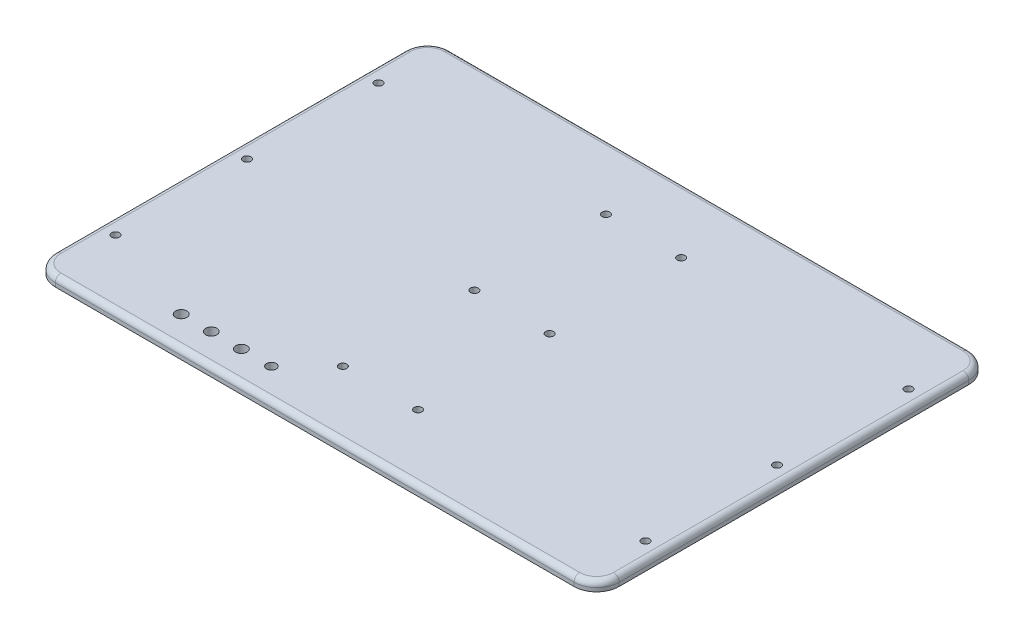
SolidWorks part; units mm, degrees
ref_plane "Front Plane" through (0, 0, 0) normal (0, 0, 1) x (1, 0, 0)
ref_plane "Top Plane" through (0, 0, 0) normal (0, 1, 0) x (1, 0, 0)
ref_plane "Right Plane" through (0, 0, 0) normal (1, 0, 0) x (0, 0, -1)
sketch "Sketch1" plane through (0, 0, 0) normal (0, 1, 0) x (1, 0, 0)
  line L1 (-150, 105) -> (150, 105)
  line L2 (-150, 105) -> (-150, -105)
  line L3 (-150, -105) -> (150, -105)
  line L4 (150, 105) -> (150, -105)
  line L5 (-150, 105) -> (150, -105) construction
  line L6 (-150, -105) -> (150, 105) construction
  point P0 (0, 0)
  dimension "D1" = 300
  dimension "D2" = 210
extrude "Boss-Extrude1" add sketch "Sketch1" along normal blind 5
fillet "Fillet1" radius 12 4 edges at (150, 2.5, -105) (150, 2.5, 105) (-150, 2.5, 105) (-150, 2.5, -105)
sketch "Sketch2" plane through (0, 5, 0) normal (0, 1, 0) x (1, 0, 0)
  line L0 (138, 105) -> (-138, 105) construction
  circle A0 centre (-141, 70) radius 2.075
  circle A1 centre (-141, 0) radius 2.075
  circle A2 centre (-141, -70) radius 2.075
  circle A3 centre (-20, 70) radius 2.075
  circle A4 centre (-20, 0) radius 2.075
  circle A5 centre (-20, -70) radius 2.075
  point P4 (0, 105)
  dimension "D3" = 4.15
  dimension "D1" = 141
  dimension "D2" = 35
  dimension "D5" = 20
  dimension "D4" = 3
extrude "Cut-Extrude1" cut sketch "Sketch2" against normal through all
mirror "Mirror1" about plane through (0, 0, 0) normal (1, 0, 0) of "Cut-Extrude1"
fillet "Fillet2" radius 3 8 edges at (146.4853, 5, -101.4853) (150, 5, 0) (146.4853, 5, 101.4853) (0, 5, 105) (-146.4853, 5, 101.4853) (-150, 5, 0) (-146.4853, 5, -101.4853) (0, 5, -105)
sketch "Sketch3" plane through (0, 5, 0) normal (0, 1, 0) x (1, 0, 0)
  line L0 (-147, 93) -> (-147, -93) construction
  line L1 (-138, -102) -> (138, -102) construction
  circle A0 centre (-87, -89) radius 3
  circle A1 centre (-71, -89) radius 3
  circle A2 centre (-55, -89) radius 3
  circle A4 centre (-39, -89) radius 2.56
  point P12 (0, 0)
  dimension "D1" = 6
  dimension "D5" = 16
  dimension "D6" = 5.12
  dimension "D2" = 60
  dimension "D3" = 13
  dimension "D4" = 3
extrude "Cut-Extrude2" cut sketch "Sketch3" against normal through all
